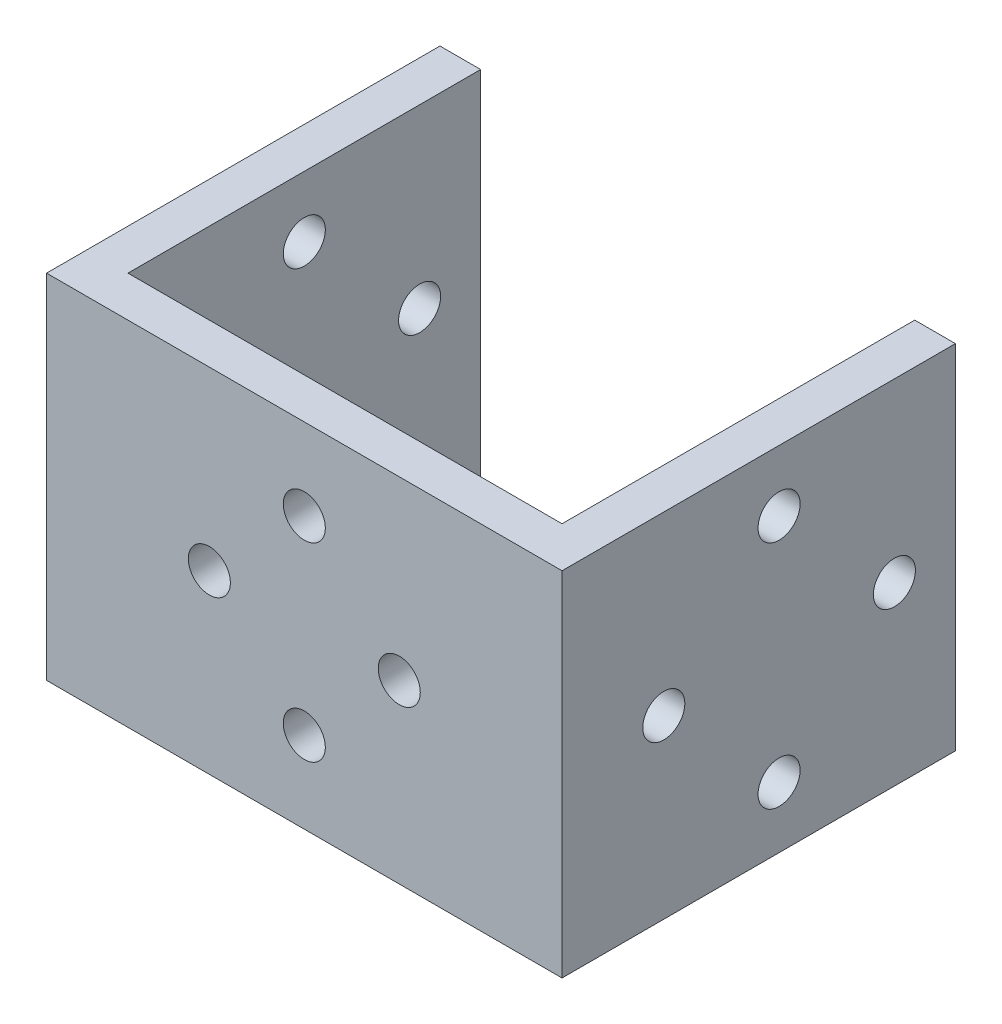
SolidWorks part; units mm, degrees
ref_plane "Front Plane" through (0, 0, 0) normal (0, 0, 1) x (1, 0, 0)
ref_plane "Top Plane" through (0, 0, 0) normal (0, 1, 0) x (1, 0, 0)
ref_plane "Right Plane" through (0, 0, 0) normal (1, 0, 0) x (0, 0, -1)
sketch "Sketch1" plane through (0, 0, 0) normal (0, 0, 1) x (1, 0, 0)
  line L0 (-7, 0) -> (7, 0) construction
  line L2 (-19, -13) -> (19, -13)
  line L3 (-19, -13) -> (-19, 13)
  line L4 (-19, 13) -> (19, 13)
  line L5 (19, -13) -> (19, 13)
  line L6 (-19, -13) -> (19, 13) construction
  line L7 (-19, 13) -> (19, -13) construction
  circle A0 centre (-7, 0) radius 1.55
  circle A2 centre (0, 7) radius 1.55
  circle A3 centre (7, 0) radius 1.55
  circle A4 centre (0, -7) radius 1.55
  point P4 (0, 0)
  point P6 (0, 0)
  point P15 (0, 0)
  dimension "D1" = 4
extrude "Boss-Extrude1" add sketch "Sketch1" along normal blind 3
sketch "Sketch2" plane through (-19, 0, 0) normal (-1, 0, 0) x (0, 0, 1)
  line L0 (3, -13) -> (3, 13)
  line L1 (3, -13) -> (-26, -13)
  line L2 (3, 13) -> (-26, 13)
  line L3 (-26, -13) -> (-26, 13)
  line L4 (0, 13) -> (0, -13) construction
  line L5 (-13, 0) -> (-4.5, 0) construction
  line L6 (0, 0) -> (-13, 0) construction
  circle A0 centre (-4.5, 0) radius 1.55
  circle A1 centre (-13, -8.5) radius 1.55
  circle A2 centre (-21.5, 0) radius 1.55
  circle A3 centre (-13, 8.5) radius 1.55
  point P23 (-13, 0)
  dimension "D1" = 4
extrude "Boss-Extrude2" add sketch "Sketch2" against normal blind 3
extrude "Boss-Extrude3" add sketch "Sketch2<2>" along normal blind 3 from surface starting at face at (19, 0, 1.5)
sketch "Sketch2<2>" plane through (-19, 0, 0) normal (-1, 0, 0) x (0, 0, 1) same geometry as "Sketch2"
